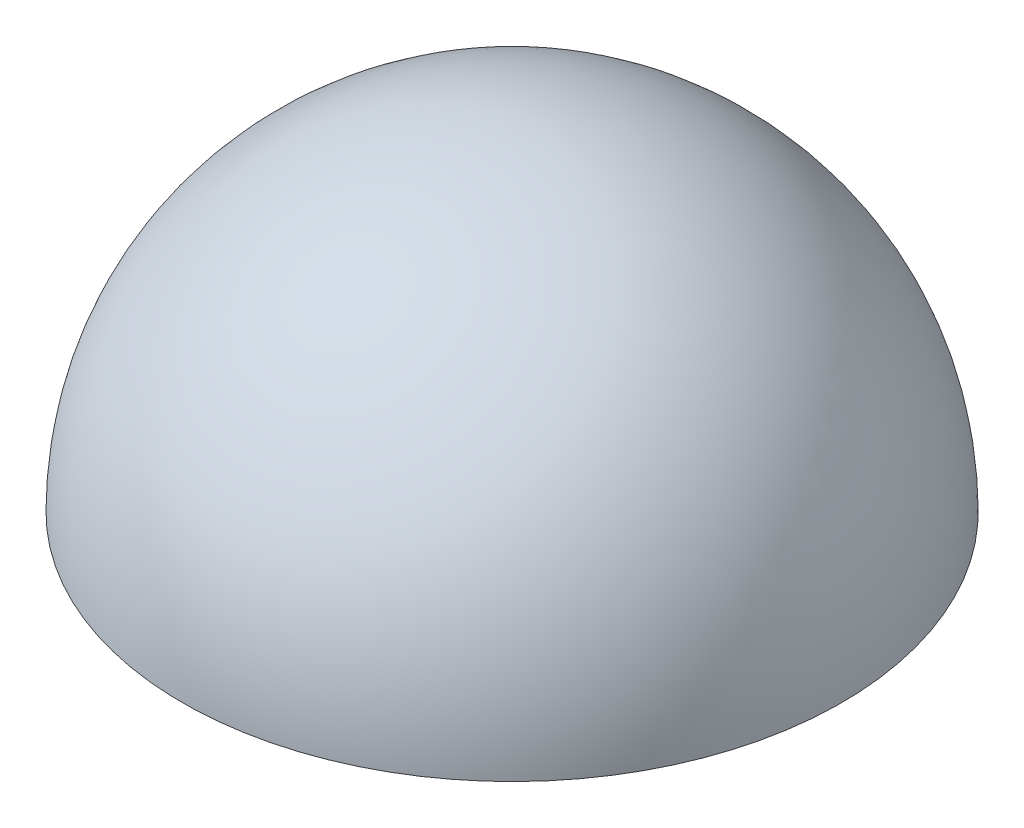
SolidWorks part; units mm, degrees
ref_plane "前视基准面" through (0, 0, 0) normal (0, 0, 1) x (1, 0, 0)
ref_plane "上视基准面" through (0, 0, 0) normal (0, 1, 0) x (1, 0, 0)
ref_plane "右视基准面" through (0, 0, 0) normal (1, 0, 0) x (0, 0, -1)
sketch "草图1" plane through (0, 0, 0) normal (0, 1, 0) x (1, 0, 0)
  line L0 (0, 0) -> (0, -94)
  arc A0 (0, 0) -> (0, -94) centre (0, -47) cw
revolve "旋转1" add sketch "草图1" angle 180 about L0
shell "抽壳3" thickness 1 removed face at (0, 0, 0)
